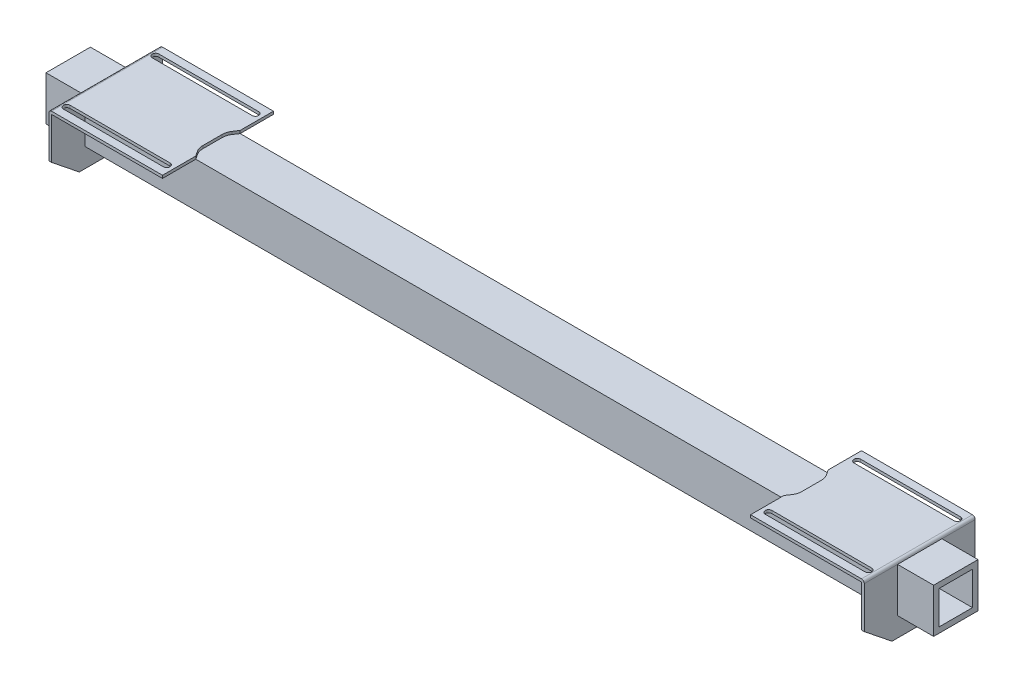
SolidWorks part; units mm, degrees
ref_plane "Front Plane" through (0, 0, 0) normal (0, 0, 1) x (1, 0, 0)
ref_plane "Top Plane" through (0, 0, 0) normal (0, 1, 0) x (1, 0, 0)
ref_plane "Right Plane" through (0, 0, 0) normal (1, 0, 0) x (0, 0, -1)
sketch "Sketch3" plane through (0, 0, 0) normal (1, 0, 0) x (0, 0, -1)
  line L1 (0, 0) -> (80, 0)
  line L2 (0, 0) -> (0, 80)
  line L3 (0, 80) -> (80, 80)
  line L4 (80, 0) -> (80, 80)
  line L5 (10, 70) -> (70, 70)
  line L6 (10, 70) -> (10, 10)
  line L7 (10, 10) -> (70, 10)
  line L8 (70, 70) -> (70, 10)
  dimension "D1" = 80
  dimension "D2" = 80
  dimension "D3" = 10
  dimension "D4" = 10
  dimension "D5" = 10
  dimension "D6" = 10
extrude "Boss-Extrude2" add sketch "Sketch3" along normal blind 1600
ref_plane "Plane1" through (1530, 0, 0) normal (1, 0, 0) x (0, 0, -1)
sketch "Sketch7" plane through (1530, 0, 0) normal (1, 0, 0) x (0, 0, -1)
  line L0 (-60, 85) -> (140, 85)
  line L1 (140, 85) -> (140, 5)
  line L2 (140, 5) -> (90, -35)
  line L3 (90, -35) -> (-10, -35)
  line L4 (-10, -35) -> (-60, 5)
  line L5 (-60, 5) -> (-60, 85)
  line L6 (80, 80) -> (0, 80) construction
  line L7 (70, 70) -> (10, 70) construction
  line L8 (70, 70) -> (10, 70)
  line L9 (70, 10) -> (70, 70) construction
  line L10 (10, 10) -> (70, 10) construction
  line L11 (10, 70) -> (10, 10) construction
  line L12 (70, 10) -> (70, 70)
  line L13 (10, 10) -> (70, 10)
  line L14 (10, 70) -> (10, 10)
  point P10 (40, 85)
  point P11 (40, 80)
  dimension "D1" = 200
  dimension "D2" = 120
  dimension "D3" = 50
  dimension "D4" = 50
  dimension "D5" = 5
  dimension "D6" = 40
extrude "Boss-Extrude3" add sketch "Sketch7" along normal blind 5
sketch "Sketch8" plane through (0, 0, -80) normal (0, 0, -1) x (-1, 0, 0)
  line L0 (-1535, 85) -> (-1530, 85) construction
  line L1 (-1535, 85) -> (-1330, 85)
  line L2 (-1535, 85) -> (-1535, 80)
  line L3 (-1535, 80) -> (-1330, 80)
  line L4 (-1330, 85) -> (-1330, 80)
  line L5 (-1535, 5) -> (-1535, 85) construction
  dimension "D1" = 5
  dimension "D2" = 205
extrude "Boss-Extrude4" add sketch "Sketch8" along normal up to surface and the other way up to surface up to face at (1532.5, 45, -140) other way up to face at (1532.5, 45, 60)
sketch "Sketch9" plane through (0, 85, 0) normal (0, 1, 0) x (1, 0, 0)
  line L0 (1330, 80) -> (1335.8013, 71.2981)
  line L1 (1330, 140) -> (1330, -60) construction
  line L2 (1340, 57.4306) -> (1340, 22.5694)
  line L3 (1335.8013, 8.7019) -> (1330, 0)
  line L4 (1330, 0) -> (0, 0) construction
  line L5 (1330, 0) -> (1330, 80)
  line L6 (1600, 80) -> (1600, 0) construction
  arc A0 (1340, 22.5694) -> (1335.8013, 8.7019) centre (1315, 22.5694) cw
  arc A1 (1335.8013, 71.2981) -> (1340, 57.4306) centre (1315, 57.4306) cw
  point P15 (1340, 15)
  point P18 (1340, 65)
  dimension "D4" = 25
  dimension "D1" = 10
  dimension "D2" = 15
  dimension "D3" = 15
extrude "Cut-Extrude1" cut sketch "Sketch9" against normal up to surface (5 mm away) up to face at (1430, 80, 30)
sketch "Sketch10" plane through (0, 85, 0) normal (0, 1, 0) x (1, 0, 0)
  line L0 (1342.5, 120) -> (1522.5, 120) construction
  line L1 (1342.5, 126) -> (1522.5, 126)
  line L2 (1342.5, 114) -> (1522.5, 114)
  line L3 (1342.5, -40) -> (1522.5, -40) construction
  line L4 (1342.5, -34) -> (1522.5, -34)
  line L5 (1342.5, -46) -> (1522.5, -46)
  line L6 (1535, 140) -> (1330, 140) construction
  arc A0 (1342.5, 126) -> (1342.5, 114) centre (1342.5, 120) ccw
  arc A1 (1522.5, 114) -> (1522.5, 126) centre (1522.5, 120) ccw
  arc A2 (1342.5, -34) -> (1342.5, -46) centre (1342.5, -40) ccw
  arc A3 (1522.5, -46) -> (1522.5, -34) centre (1522.5, -40) ccw
  point P2 (1432.5, 120)
  point P7 (1432.5, -40)
  point P16 (1432.5, 140)
  point P17 (1432.5, 126)
  dimension "D1" = 180
  dimension "D2" = 12
  dimension "D3" = 12
  dimension "D4" = 160
  dimension "D5" = 20
extrude "Cut-Extrude2" cut sketch "Sketch10" against normal up to next
fillet "Fillet1" radius 5 1 edges at (1535, 85, -40)
ref_plane "Plane2" through (800, 0, 0) normal (1, 0, 0) x (0, 0, -1)
mirror "Mirror1" about plane through (800, 0, 0) normal (1, 0, 0) of "Fillet1", "Boss-Extrude3"
mirror "Mirror2" about plane through (800, 0, 0) normal (1, 0, 0) of "Fillet1", "Cut-Extrude2", "Boss-Extrude3", "Boss-Extrude4", "Cut-Extrude1"
sketch "Sketch13" plane through (0, 0, 0) normal (0, 0, 1) x (1, 0, 0)
  line L0 (0, 40) -> (2446.8223, 40) construction
  line L1 (0, 80) -> (0, 0) construction
sketch "Sketch14" plane through (0, 80, 0) normal (0, 1, 0) x (1, 0, 0)
  line L0 (800, 80) -> (800, 0) construction
  line L1 (1530, 80) -> (70, 80) construction
  line L2 (1530, 0) -> (70, 0) construction
  line L3 (706.4267, 40) -> (893.5733, 40) construction
  point P8 (800, 40)
equation "\"D2@Sketch3\"=\"D1@Sketch3\""
equation "\"D4@Sketch3\"=\"D3@Sketch3\""
equation "\"D5@Sketch3\"=\"D3@Sketch3\""
equation "\"D6@Sketch3\"=\"D3@Sketch3\""
equation "\"D3@Sketch9\"=\"D2@Sketch9\""
